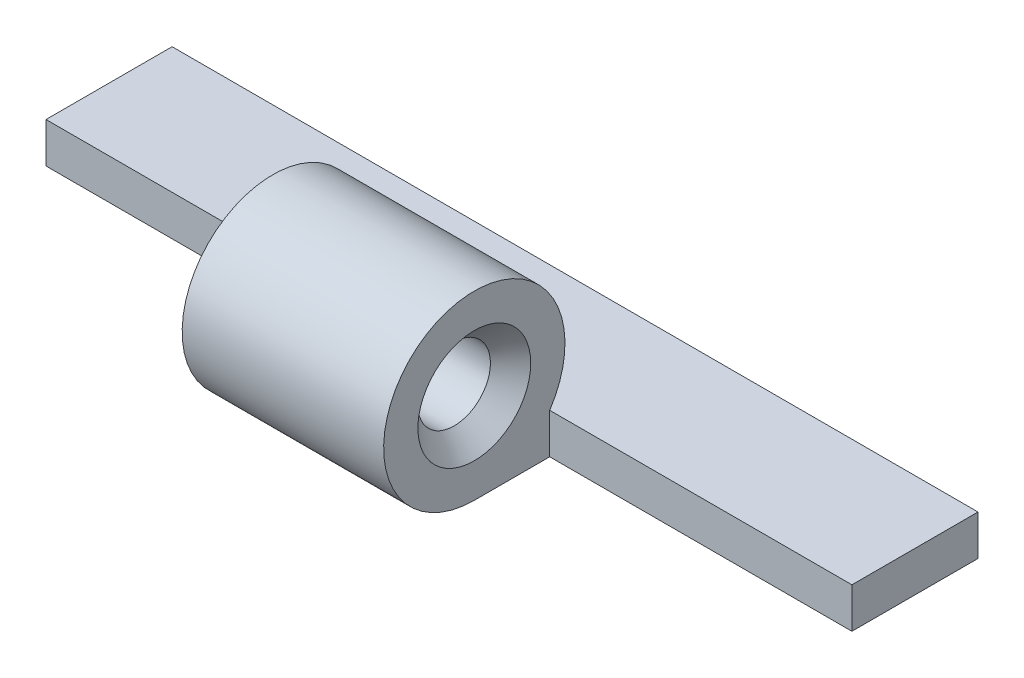
SolidWorks part; units mm, degrees
ref_plane "Ebene vorne" through (0, 0, 0) normal (0, 0, 1) x (1, 0, 0)
ref_plane "Ebene oben" through (0, 0, 0) normal (0, 1, 0) x (1, 0, 0)
ref_plane "Ebene rechts" through (0, 0, 0) normal (1, 0, 0) x (0, 0, -1)
sketch "Skizze2" plane through (0, 0, 0) normal (0, 1, 0) x (1, 0, 0)
  line L1 (-7.5, 2.5) -> (7.5, 2.5)
  line L2 (-7.5, 2.5) -> (-7.5, -2.5)
  line L3 (-7.5, -2.5) -> (7.5, -2.5)
  line L4 (7.5, 2.5) -> (7.5, -2.5)
  line L5 (-7.5, 2.5) -> (7.5, -2.5) construction
  line L6 (-7.5, -2.5) -> (7.5, 2.5) construction
  point P0 (0, 0)
  dimension "D1" = 15
  dimension "D2" = 5
extrude "Aufsatz-Linear austragen1" add sketch "Skizze2" along normal blind 1
sketch "Skizze3" plane through (7.5, 0, 0) normal (1, 0, 0) x (0, 0, -1)
  circle A0 centre (-2.5, 2.25) radius 2.25
  circle A1 centre (-2.5, 2.25) radius 0.9
  dimension "D1" = 1.8
  dimension "D2" = 4.5
extrude "Aufsatz-Linear austragen2" add sketch "Skizze3" against normal up to surface (15 mm away) up to face at (-7.5, 0.5, 0)
ref_plane "Tangential Ebene" through (0, 0, 0.25) normal (0, 0, -1) x (-1, 0, 0)
sketch "Skizze5" plane through (7.5, 0, 0) normal (1, 0, 0) x (0, 0, -1)
  line L0 (-0.6292, 1) -> (-0.6292, 0)
  line L1 (-0.6292, 0) -> (-2.5, 0)
  line L3 (2.5, 1) -> (-0.6292, 1)
  line L4 (-2.5, 0) -> (2.5, 0)
  line L5 (2.5, 0) -> (2.5, 1)
  line L6 (2.5, 1) -> (-0.6292, 1) construction
  line L7 (-2.5, 0) -> (2.5, 0) construction
  line L8 (2.5, 0) -> (2.5, 1) construction
  arc A1 (-0.6292, 1) -> (-2.5, 0) centre (-2.5, 2.25) ccw
  arc A2 (-0.6292, 1) -> (-2.5, 0) centre (-2.5, 2.25) ccw
  dimension "D1" = 0
extrude "Schnitt-Linear austragen1" cut sketch "Skizze5" against normal blind 5
pattern_linear "Lineares Muster1" count 2 spacing 10 along (-1, 0, 0) of "Schnitt-Linear austragen1"
ref_plane "Spiegelebene" through (0, 0, 0) normal (1, 0, 0) x (0, 0, -1)
sketch "Skizze7" plane through (7.5, 0, 0) normal (1, 0, 0) x (0, 0, -1)
  line L1 (2.5, 1) -> (-0.6292, 1)
  line L2 (2.5, 1) -> (2.5, 0)
  line L3 (2.5, 0) -> (-0.6292, 0)
  line L4 (-0.6292, 1) -> (-0.6292, 0)
extrude "Verbreiterung" add sketch "Skizze7" along normal blind 2.5
mirror "Spiegeln1" about plane through (0, 0, 0) normal (1, 0, 0) of "Verbreiterung"
ref_axis "Achse1" through (-2.5, 2.25, 2.5) along (1, 0, 0)
chamfer "Fase1" distance 0.5 angle 45 2 edges at (-2.5, 2.25, 1.6) (2.5, 2.25, 1.6)
